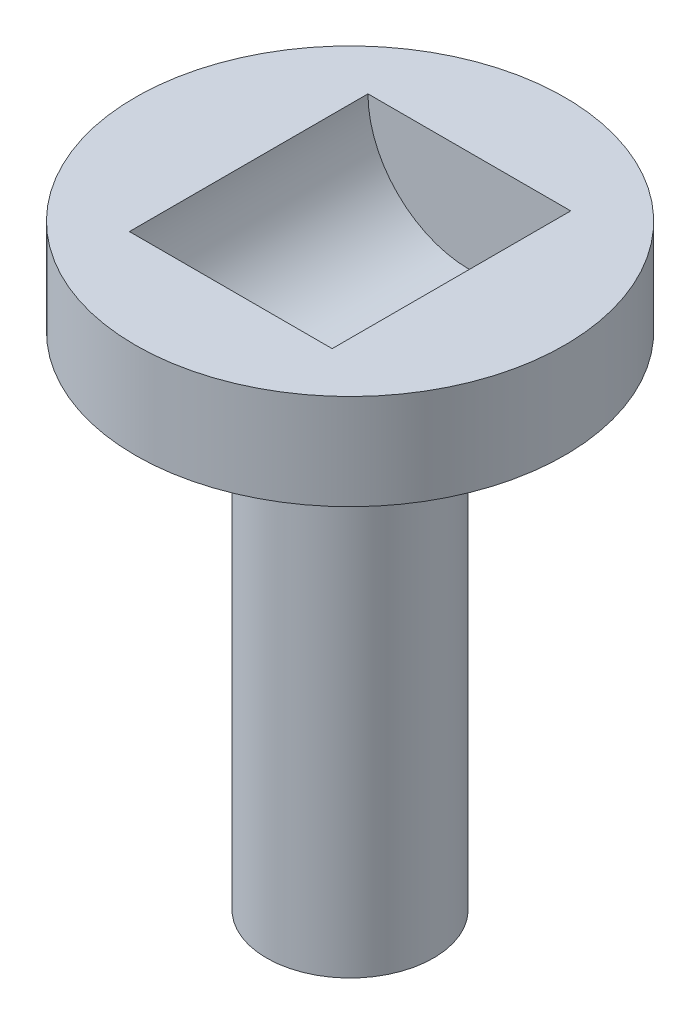
SolidWorks part; units mm, degrees
ref_plane "Alzado" through (0, 0, 0) normal (0, 0, 1) x (1, 0, 0)
ref_plane "Planta" through (0, 0, 0) normal (0, 1, 0) x (1, 0, 0)
ref_plane "Vista lateral" through (0, 0, 0) normal (1, 0, 0) x (0, 0, -1)
sketch "Croquis2" plane through (0, 0, 0) normal (0, 1, 0) x (1, 0, 0)
  circle A0 centre (0, 0) radius 3.5
  dimension "D1" = 7
extrude "Saliente-Extruir1" add sketch "Croquis2" along normal blind 20
sketch "Croquis3" plane through (0, 20, 0) normal (0, 1, 0) x (1, 0, 0)
  circle A0 centre (0, 0) radius 7.5
  dimension "D1" = 15
extrude "Saliente-Extruir2" add sketch "Croquis3" along normal blind 1
sketch "Croquis5" plane through (0, 21, 0) normal (0, 1, 0) x (1, 0, 0)
  circle A0 centre (0, 0) radius 9
  dimension "D1" = 18
extrude "Saliente-Extruir3" add sketch "Croquis5" along normal blind 4
sketch "Croquis6" plane through (0, 0, 0) normal (0, 0, 1) x (1, 0, 0)
  line L0 (9, 25) -> (-9, 25) construction
  circle A0 centre (0, 25) radius 4.25
  dimension "D1" = 8.5
extrude "Cortar-Extruir1" cut sketch "Croquis6" against normal blind 5 and the other way blind 5
sketch "Croquis7" plane through (0, 0, 0) normal (0, -1, 0) x (1, 0, 0)
  circle A0 centre (0, 0) radius 0.75
  dimension "D1" = 1.5
extrude "Cortar-Extruir2" cut sketch "Croquis7" against normal blind 5
